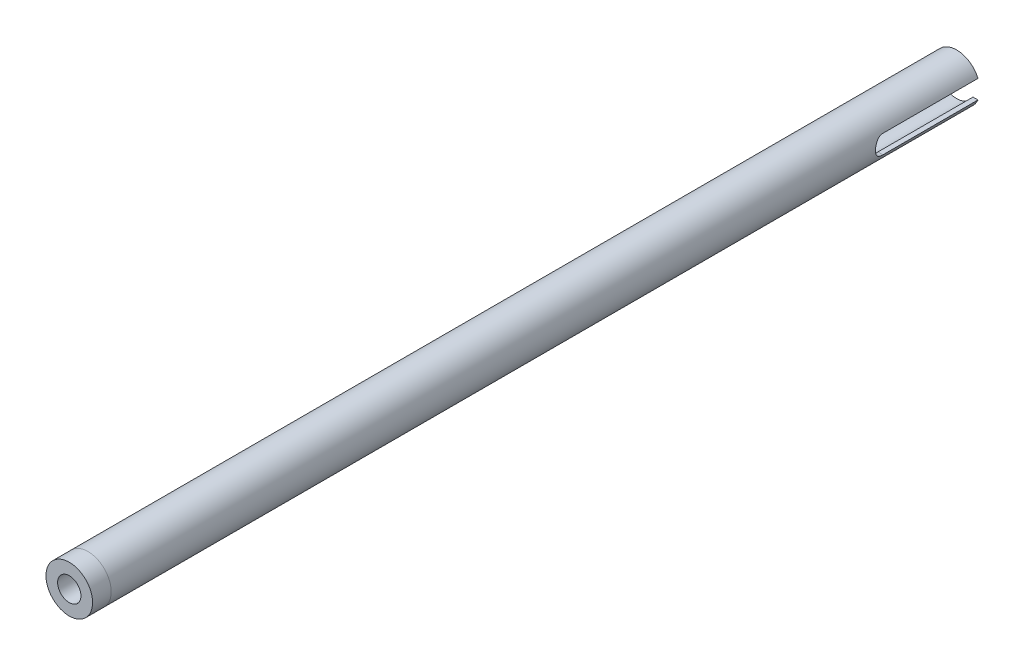
SolidWorks part; units mm, degrees
ref_plane "Front Plane" through (0, 0, 0) normal (0, 0, 1) x (1, 0, 0)
ref_plane "Top Plane" through (0, 0, 0) normal (0, 1, 0) x (1, 0, 0)
ref_plane "Right Plane" through (0, 0, 0) normal (1, 0, 0) x (0, 0, -1)
sketch "Axis" plane through (0, 0, 0) normal (0, 1, 0) x (1, 0, 0)
  line L0 (0, 0) -> (0, 302.1575) construction
  line L1 (0, 0) -> (0, -28.575) construction
  line L2 (0, 302.1575) -> (-7.9375, 302.1575) construction
  line L3 (0, 325.4918) -> (-31.242, 233.648) construction
  dimension "D1" = 28.575
  dimension "D2" = 7.9375
sketch "Sketch1" plane through (0, 0, 0) normal (0, 0, 1) x (1, 0, 0)
  line L0 (-7.9375, 0) -> (7.9375, 0) construction
  line L1 (-7.2748, 3.175) -> (7.2748, 3.175)
  line L2 (-7.2748, -3.175) -> (7.2748, -3.175)
  circle A0 centre (0, 0) radius 7.9375
  circle A1 centre (0, 0) radius 6.4135
  circle A2 centre (0, 0) radius 3.9688
  dimension "D1" = 15.875
  dimension "D3" = 7.9375
  dimension "D2" = 1.524
  dimension "D4" = 6.35
extrude "Threaded insert 1-1" add sketch "Sketch1" against normal blind 6.35 contours A2 L1 A1 | A1 L1 A0 | A2 L0 A1 L1 | A1 L0 A0 L1 | L0 A1 L2 A0 | L0 A2 L2 A1 | A2 L2 A1 | A1 L2 A0 | L0 A1 L2 A2 | L0 A0 L2 A1 | A0 L0 A1 L1 | A1 L0 A2 L1 region at (4.7887, 1.6543, 0) region at (4.7887, -1.6543, 0) region at (6.9234, 1.6163, 0) region at (6.9234, -1.6163, 0) region at (-4.7887, -1.6543, 0) region at (-4.7887, 1.6543, 0) region at (0, 4.6159, 0) region at (0, -4.6159, 0) region at (0, 6.5666, 0) region at (6.4237, -3.3281, 0) region at (-6.9234, -1.6163, 0) region at (-6.9234, 1.6163, 0)
extrude "Threaded insert 1-2" add sketch "Sketch1<3>" against normal blind 9.525 from surface contours A2 L1 A1 | A2 L0 A1 L1 | L0 A2 L2 A1 | A2 L2 A1 | L0 A1 L2 A2 | A1 L0 A2 L1 region at (4.7887, 1.6543, 0) region at (4.7887, -1.6543, 0) region at (-4.7887, -1.6543, 0) region at (-4.7887, 1.6543, 0) region at (0, 4.6159, 0) region at (0, -4.6159, 0) starting at face at (7.9375, 0, -6.35)
sketch "Sketch1<3>" plane through (0, 0, 0) normal (0, 0, 1) x (1, 0, 0) same geometry as "Sketch1"
extrude "A-arm tube" add sketch "Sketch1<4>" against normal up to vertex (302.1575 mm away) from surface separate body contours A1 L1 A0 | A1 L0 A0 L1 | L0 A1 L2 A0 | A1 L2 A0 | L0 A0 L2 A1 | A0 L0 A1 L1 region at (6.9234, 1.6163, 0) region at (6.9234, -1.6163, 0) region at (0, 6.5666, 0) region at (6.4237, -3.3281, 0) region at (-6.9234, -1.6163, 0) region at (-6.9234, 1.6163, 0) up to point (0, 0, -302.1575) starting at face at (6.4135, 0, -6.35)
sketch "Sketch1<4>" plane through (0, 0, 0) normal (0, 0, 1) x (1, 0, 0) same geometry as "Sketch1"
extrude "Apex slot" cut sketch "Sketch1<5>" along normal blind 35.56 from surface contours A0 L0 A1 L1 | L0 A0 L2 A1 | A1 L0 A0 L1 | L0 A1 L2 A0 region at (6.9234, 1.6163, 0) region at (6.9234, -1.6163, 0) region at (-6.9234, -1.6163, 0) region at (-6.9234, 1.6163, 0) starting at face at (6.4135, 0, -302.1575)
sketch "Sketch1<5>" plane through (0, 0, 0) normal (0, 0, 1) x (1, 0, 0) same geometry as "Sketch1"
fillet "Fillet1" radius 3.175 4 edges at (-6.4237, 3.175, -266.5975) (-6.4237, -3.175, -266.5975) (6.4237, -3.175, -266.5975) (6.4237, 3.175, -266.5975)
equation "\"tube diameter\"= 5 / 8"
equation "\"tube thickness\"= .06"
equation "\"apex thickness\"= .25"
equation "\"tube slot\"= 1.4"
equation "\"D1@Sketch1\"=\"tube diameter\""
equation "\"D2@Sketch1\"=\"tube thickness\""
equation "\"threaded insert hole\"= .3125"
equation "\"D3@Sketch1\"=\"threaded insert hole\""
equation "\"D4@Sketch1\"=\"apex thickness\""
equation "\"D1@Apex slot\" = \"tube slot\""
equation "\"D1@Fillet1\"=\"apex thickness\"/2"
equation "\"D2@Axis\"=\"tube diameter\"/2"
